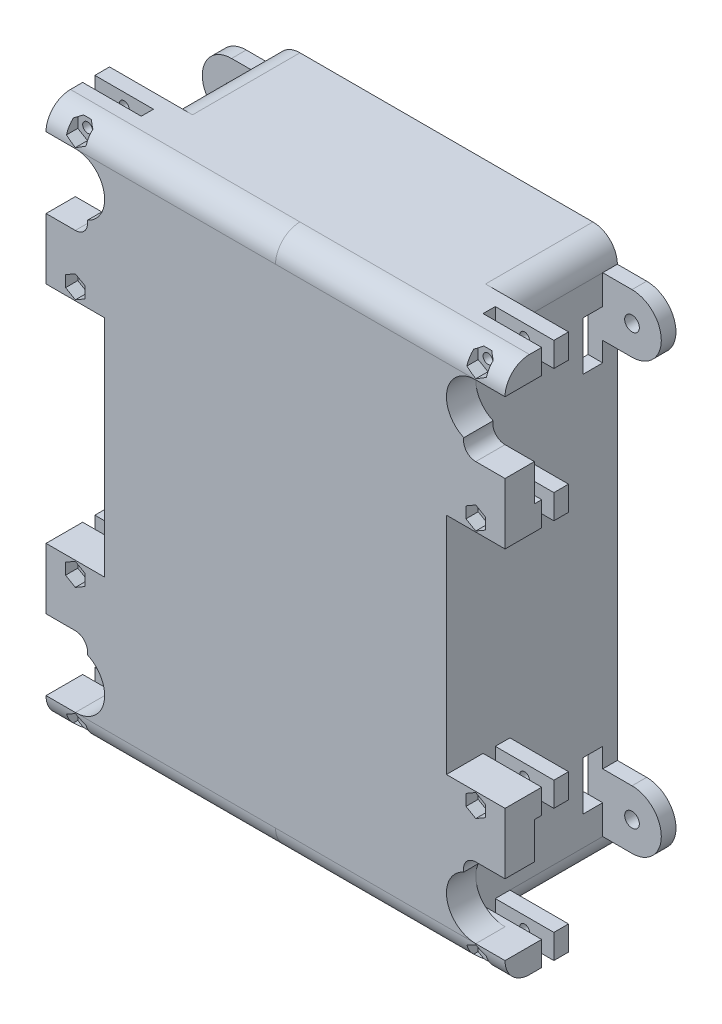
SolidWorks part; units mm, degrees
other "标注1"
sketch "草图35" plane through (-29.5, -27.5, 0) normal (-1, 0, 0) x (0, 1, 0)
ref_plane "前视基准面" through (0, 0, 0) normal (0, 0, 1) x (1, 0, 0)
ref_plane "上视基准面" through (0, 0, 0) normal (0, 1, 0) x (1, 0, 0)
ref_plane "右视基准面" through (0, 0, 0) normal (1, 0, 0) x (0, 0, -1)
sketch "草图3" plane through (0, 0, 0) normal (0, 0, 1) x (1, 0, 0)
  line L1 (17.5, -27.5) -> (-17.5, -27.5)
  line L2 (17.5, -27.5) -> (17.5, 27.5)
  line L3 (17.5, 27.5) -> (-17.5, 27.5)
  line L4 (-17.5, -27.5) -> (-17.5, -4.5)
  line L7 (-17.5, 27.5) -> (-29.5, 27.5)
  line L9 (-17.5, -4.5) -> (-29.5, -4.5)
  line L10 (-29.5, 27.5) -> (-29.5, -4.5)
  point P0 (0, 0)
  dimension "D1" = 55
  dimension "D2" = 35
  dimension "D3" = 32
  dimension "D4" = 12
extrude "凸台-拉伸3" add sketch "草图3" along normal blind 35
sketch "草图4" plane through (0, 0, 35) normal (0, 0, 1) x (1, 0, 0)
  line L1 (17.5, -27.5) -> (-12.5, -27.5)
  line L2 (17.5, -27.5) -> (17.5, 22.5)
  line L3 (17.5, 22.5) -> (-12.5, 22.5)
  line L4 (-12.5, -27.5) -> (-12.5, 22.5)
  dimension "D1" = 50
  dimension "D2" = 30
extrude "切除-拉伸1" cut sketch "草图4" against normal through all
sketch "草图5" plane through (0, 0, 35) normal (0, 0, 1) x (1, 0, 0)
  line L0 (-23.5, 22.5) -> (-29.5, 22.5)
  line L9 (-23.5, 8) -> (-29.5, 8)
  line L10 (-29.5, 27.5) -> (-29.5, -4.5) construction
  circle A1 centre (-23.5, 16.5) radius 1.25
  arc A2 (-21.0549, 11.0208) -> (-23.5, 22.5) centre (-23.5, 16.5) ccw
  arc A3 (-23.5, 8) -> (-21.0549, 11.0208) centre (-23.5, 10.5) ccw
  line M14 (-29.5, 27.5) -> (-29.5, -4.5)
  dimension "D7" = 2.5
  dimension "D1" = 5
  dimension "D6" = 6
extrude "切除-拉伸5" cut sketch "草图5" against normal blind 6 contours L9 A3 A2 L0 A1 M14 region at (-24.2708, 15.4863, 35)
sketch "草图6" plane through (0, 0, 35) normal (0, 0, 1) x (1, 0, 0)
  circle A0 centre (-23.5, 16.5) radius 1.25
extrude "切除-拉伸6" cut sketch "草图6" against normal through all
sketch "草图7" plane through (0, 0, 29) normal (0, 0, 1) x (1, 0, 0)
  line L1 (-29.5, 27.5) -> (-17.5, 27.5)
  line L2 (-29.5, 27.5) -> (-29.5, -4.5)
  line L3 (-29.5, -4.5) -> (-17.5, -4.5)
  line L4 (-17.5, 27.5) -> (-17.5, -4.5)
  dimension "D1" = 32
  dimension "D2" = 12
extrude "切除-拉伸7" cut sketch "草图7" against normal blind 4
sketch "草图9" plane through (0, 0, 25) normal (0, 0, 1) x (1, 0, 0)
  line L1 (-29.5, 22.5) -> (-17.5, 22.5)
  line L2 (-29.5, 22.5) -> (-29.5, 0.5)
  line L3 (-29.5, 0.5) -> (-17.5, 0.5)
  line L4 (-17.5, 22.5) -> (-17.5, 0.5)
  dimension "D1" = 22
  dimension "D2" = 12
extrude "切除-拉伸9" cut sketch "草图9" against normal blind 22
sketch "草图10" plane through (-29.5, 0, 0) normal (-1, 0, 0) x (0, 0, 1)
  line L1 (24, -4.5) -> (6, -4.5)
  line L2 (24, -4.5) -> (24, 27.5)
  line L3 (24, 27.5) -> (6, 27.5)
  line L4 (6, -4.5) -> (6, 27.5)
  line L6 (25, -4.5) -> (0, -4.5) construction
  line L7 (25, 27.5) -> (0, 27.5) construction
  dimension "D1" = 32
  dimension "D2" = 18
extrude "切除-拉伸10" cut sketch "草图10" against normal blind 12
sketch "草图11" plane through (0, 0, 3) normal (0, 0, 1) x (1, 0, 0)
  circle A0 centre (-23.5, 16.5) radius 1.5
  dimension "D1" = 3
extrude "切除-拉伸11" cut sketch "草图11" against normal blind 12
sketch "草图14" plane through (-17.5, 0, 0) normal (-1, 0, 0) x (0, 0, 1)
  line L1 (29, 27.5) -> (27.5, 27.5)
  line L2 (29, 27.5) -> (29, 22.5)
  line L3 (29, 22.5) -> (27.5, 22.5)
  line L4 (27.5, 27.5) -> (27.5, 22.5)
  line L5 (29, -4.5) -> (27.5, -4.5)
  line L6 (29, -4.5) -> (29, 0.5)
  line L7 (29, 0.5) -> (27.5, 0.5)
  line L8 (27.5, -4.5) -> (27.5, 0.5)
  dimension "D1" = 5
  dimension "D2" = 1.5
  dimension "D3" = 5
  dimension "D4" = 1.5
extrude "凸台-拉伸4" add sketch "草图14" along normal blind 12
sketch "草图15" plane through (0, 0, 6) normal (0, 0, 1) x (1, 0, 0)
  line L1 (-17.5, 27.5) -> (-29.5, 27.5)
  line L2 (-17.5, 27.5) -> (-17.5, 22.5)
  line L3 (-17.5, 22.5) -> (-29.5, 22.5)
  line L4 (-29.5, 27.5) -> (-29.5, 22.5)
  line L5 (-17.5, 0.5) -> (-29.5, 0.5)
  line L6 (-17.5, 0.5) -> (-17.5, -4.5)
  line L7 (-17.5, -4.5) -> (-29.5, -4.5)
  line L8 (-29.5, 0.5) -> (-29.5, -4.5)
  dimension "D1" = 5
  dimension "D2" = 12
  dimension "D3" = 5
  dimension "D4" = 12
extrude "切除-拉伸15" cut sketch "草图15" against normal blind 12
sketch "草图16" plane through (0, 0, 24) normal (0, 0, -1) x (-1, 0, 0)
  line L1 (17.5, 27.5) -> (29.5, 27.5)
  line L2 (17.5, 27.5) -> (17.5, 22.5)
  line L3 (17.5, 22.5) -> (29.5, 22.5)
  line L4 (29.5, 27.5) -> (29.5, 22.5)
  line L5 (29.5, 0.5) -> (17.5, 0.5)
  line L6 (29.5, 0.5) -> (29.5, -4.5)
  line L7 (29.5, -4.5) -> (17.5, -4.5)
  line L8 (17.5, 0.5) -> (17.5, -4.5)
  dimension "D1" = 5
  dimension "D2" = 12
  dimension "D3" = 5
  dimension "D4" = 12
extrude "凸台-拉伸5" add sketch "草图16" along normal blind 2
sketch "草图17" plane through (0, 0, 22) normal (0, 0, -1) x (-1, 0, 0)
  line L0 (29.5, 27.5) -> (17.5, 27.5) construction
  line L1 (17.5, 22.5) -> (17.5, 27.5) construction
  line L2 (-970.5, 11.5) -> (49029.5, 11.5) construction
  line L3 (29.5, 22.5) -> (29.5, 0.5) construction
  circle A0 centre (23.5, 25) radius 1
  circle A1 centre (23.5, -2) radius 1
  point P11 (29.5, 11.5)
  dimension "D1" = 2.5
  dimension "D2" = 6
  dimension "D3" = 2
extrude "切除-拉伸16" cut sketch "草图17" against normal through all
sketch "草图18" plane through (-12.5, 0, 0) normal (1, 0, 0) x (0, 0, -1)
  line L1 (-35, 22.5) -> (-30, 22.5)
  line L2 (-35, 22.5) -> (-35, -27.5)
  line L3 (-35, -27.5) -> (-30, -27.5)
  line L4 (-30, 22.5) -> (-30, -27.5)
  line L5 (0, -27.5) -> (-35, -27.5) construction
  dimension "D1" = 50
  dimension "D2" = 5
extrude "凸台-拉伸6" add sketch "草图18" along normal blind 30
sketch "草图19" plane through (-17.5, 0, 0) normal (-1, 0, 0) x (0, 0, 1)
  line L0 (3, 11.5) -> (50003, 11.5) construction
  line L1 (3, 0.5) -> (3, 22.5) construction
  line L3 (3, 16.5) -> (7, 16.5)
  line L4 (3, 16.5) -> (3, 6.5)
  line L5 (3, 6.5) -> (7, 6.5)
  line L6 (7, 16.5) -> (7, 6.5)
  point P4 (3, 11.5)
  dimension "D1" = 10
  dimension "D2" = 4
  dimension "D3" = 5
extrude "切除-拉伸17" cut sketch "草图19" against normal blind 30
fillet "圆角1" radius 5 1 edges at (-17.5, 27.5, 11)
sketch "草图20" plane through (0, 0, 3) normal (0, 0, 1) x (1, 0, 0)
  line L1 (-29.5, 0.5) -> (-17.5, 0.5)
  line L2 (-29.5, 0.5) -> (-29.5, 6.5)
  line L3 (-29.5, 6.5) -> (-17.5, 6.5)
  line L4 (-17.5, 0.5) -> (-17.5, 6.5)
  dimension "D1" = 6
  dimension "D2" = 12
extrude "切除-拉伸18" cut sketch "草图20" against normal blind 30
sketch "草图21" plane through (0, 0, 30) normal (0, 0, -1) x (-1, 0, 0)
  line L1 (-17.5, -27.5) -> (14.5, -27.5)
  line L2 (-17.5, -27.5) -> (-17.5, 24.5)
  line L3 (-17.5, 24.5) -> (14.5, 24.5)
  line L4 (14.5, -27.5) -> (14.5, 24.5)
  dimension "D1" = 52
  dimension "D2" = 32
extrude "切除-拉伸19" cut sketch "草图21" along normal blind 54
fillet "圆角3" radius 5 1 edges at (-6, 27.5, 35)
sketch "草图23" plane through (0, 0, 0) normal (0, 0, -1) x (-1, 0, 0)
  line L1 (29.5, 22.5) -> (17.5, 22.5) construction
  line L2 (29.5, 22.5) -> (29.5, 6.5) construction
  line L3 (23.5, 22.5) -> (29.5, 22.5)
  line L4 (29.5, 22.5) -> (29.5, 16.5)
  arc A0 (29.5, 16.5) -> (23.5, 22.5) centre (23.5, 16.5) ccw
extrude "切除-拉伸21" cut sketch "草图23" against normal blind 12
sketch "草图24" plane through (0, 0, 0) normal (0, 0, -1) x (-1, 0, 0)
  line L0 (17.5, 6.5) -> (17.5, 10.5)
  line L1 (23.5, 10.5) -> (17.5, 10.5)
  line L2 (29.5, 16.5) -> (29.5, 6.5) construction
  line L3 (17.5, 6.5) -> (29.5, 6.5)
  line L4 (29.5, 6.5) -> (29.5, 16.5)
  arc A0 (23.5, 10.5) -> (29.5, 16.5) centre (23.5, 16.5) ccw
extrude "切除-拉伸22" cut sketch "草图24" against normal blind 12
sketch "草图26" plane through (-14.5, 0, 0) normal (1, 0, 0) x (0, 0, -1)
  line L1 (-7, 16.5) -> (-3, 16.5)
  line L2 (-7, 16.5) -> (-7, 24.5)
  line L3 (-7, 24.5) -> (-3, 24.5)
  line L4 (-3, 16.5) -> (-3, 24.5)
  line L5 (0, 24.5) -> (-30, 24.5) construction
  dimension "D1" = 8
  dimension "D2" = 4
extrude "凸台-拉伸7" add sketch "草图26" along normal blind 8
sketch "草图27" plane through (0, 0, 3) normal (0, 0, -1) x (-1, 0, 0)
  line L0 (6.5, 24.5) -> (14.5, 24.5) construction
  line L1 (14.5, 16.5) -> (14.5, 24.5) construction
  circle A0 centre (10.5, 20.5) radius 1.5
  dimension "D1" = 3
  dimension "D2" = 4
  dimension "D3" = 4
extrude "切除-拉伸23" cut sketch "草图27" against normal blind 8
sketch "草图32" plane through (0, 0, 3) normal (0, 0, -1) x (-1, 0, 0)
  line L0 (6.5, 20.5) -> (6.5, 16.5)
  line L1 (6.5, 16.5) -> (10.5, 16.5)
  line L2 (6.5, 24.5) -> (6.5, 20.5)
  line L3 (10.5, 24.5) -> (6.5, 24.5)
  arc A0 (6.5, 20.5) -> (10.5, 16.5) centre (10.5, 20.5) ccw
  arc A1 (10.5, 24.5) -> (10.5, 16.5) centre (10.5, 20.5) ccw
  line M6 (14.5, 24.5) -> (6.5, 24.5)
  line M7 (6.5, 24.5) -> (6.5, 16.5)
extrude "切除-拉伸25" cut sketch "草图32" against normal blind 10 contours A1 M6 M7 region at (-7.3935, 23.6065, 3)
sketch "草图33" plane through (0, 0, 3) normal (0, 0, -1) x (-1, 0, 0)
  line L0 (6.5, 20.5) -> (6.5, 16.5)
  line L1 (6.5, 16.5) -> (10.5, 16.5)
  arc A0 (6.5, 20.5) -> (10.5, 16.5) centre (10.5, 20.5) ccw
extrude "切除-拉伸26" cut sketch "草图33" against normal blind 10
sketch "草图34" plane through (0, 0, 7) normal (0, 0, 1) x (1, 0, 0)
  line L0 (-14.5, 24.5) -> (-14.5, 16.5) construction
  line L1 (-10.5, 17.44) -> (-7.85, 18.97)
  line L2 (-7.85, 18.97) -> (-7.85, 22.03)
  line L3 (-7.85, 22.03) -> (-10.5, 23.56)
  line L4 (-10.5, 23.56) -> (-13.15, 22.03)
  line L5 (-13.15, 22.03) -> (-13.15, 18.97)
  line L6 (-13.15, 18.97) -> (-10.5, 17.44)
  circle A0 centre (-10.5, 20.5) radius 2.65 construction
  dimension "D1" = 5.3
extrude "切除-拉伸27" cut sketch "草图34" against normal blind 2
sketch "草图36" plane through (0, 0, 35) normal (0, 0, 1) x (1, 0, 0)
  line L0 (-29.5, 8) -> (-29.5, -4.5) construction
  line L1 (-23.5, 27.3094) -> (-25.5, 26.1547)
  line L2 (-25.5, 26.1547) -> (-25.5, 23.8453)
  line L3 (-25.5, 23.8453) -> (-23.5, 22.6906)
  line L4 (-23.5, 22.6906) -> (-21.5, 23.8453)
  line L5 (-21.5, 23.8453) -> (-21.5, 26.1547)
  line L6 (-21.5, 26.1547) -> (-23.5, 27.3094)
  line L7 (-23.5, 0.3094) -> (-25.5, -0.8453)
  line L8 (-25.5, -0.8453) -> (-25.5, -3.1547)
  line L9 (-25.5, -3.1547) -> (-23.5, -4.3094)
  line L10 (-23.5, -4.3094) -> (-21.5, -3.1547)
  line L11 (-21.5, -3.1547) -> (-21.5, -0.8453)
  line L12 (-21.5, -0.8453) -> (-23.5, 0.3094)
  line L13 (-29.5, 27.5) -> (-29.5, 22.5) construction
  circle A0 centre (-23.5, 25) radius 2 construction
  circle A1 centre (-23.5, -2) radius 2 construction
  dimension "D1" = 4
  dimension "D2" = 4
extrude "切除-拉伸28" cut sketch "草图36" against normal blind 2.5
sketch "草图37" plane through (0, 0, 22) normal (0, 0, -1) x (-1, 0, 0)
  circle A0 centre (23.5, 25) radius 1.5
  circle A1 centre (23.5, -2) radius 1.5
  dimension "D1" = 3
extrude "切除-拉伸29" cut sketch "草图37" against normal blind 1
mirror "镜向5" about plane through (17.5, -27.5, 35) normal (0, 1, 0) of "切除-拉伸1", "切除-拉伸5", "切除-拉伸6", "切除-拉伸7", "切除-拉伸9", "切除-拉伸10", "切除-拉伸11", "凸台-拉伸4", "切除-拉伸15", "凸台-拉伸5", "切除-拉伸16", "凸台-拉伸6", "切除-拉伸17", "圆角1", "切除-拉伸18", "切除-拉伸19", "圆角3", "切除-拉伸21", "切除-拉伸22", "凸台-拉伸7", "切除-拉伸23", "切除-拉伸25", "切除-拉伸26", "切除-拉伸27", "切除-拉伸28", "凸台-拉伸3", "切除-拉伸29"
ref_plane "基准面12" through (17.5, 0, 0) normal (-1, 0, 0) x (0, 0, 1)
mirror "镜向8" about plane through (17.5, 0, 0) normal (-1, 0, 0) of "切除-拉伸1", "切除-拉伸5", "切除-拉伸6", "切除-拉伸7", "切除-拉伸9", "切除-拉伸10", "切除-拉伸11", "凸台-拉伸4", "切除-拉伸15", "凸台-拉伸5", "切除-拉伸16", "凸台-拉伸6", "切除-拉伸17", "圆角1", "切除-拉伸18", "切除-拉伸19", "圆角3", "切除-拉伸21", "切除-拉伸22", "凸台-拉伸7", "切除-拉伸23", "切除-拉伸25", "切除-拉伸26", "切除-拉伸27", "切除-拉伸28", "凸台-拉伸3", "切除-拉伸29"
pattern_circular "阵列(圆周)1" count 2 over 360 about axis through (17.5, -27.5, 35) along (0, 0, -1) of "凸台-拉伸3", "切除-拉伸28", "切除-拉伸27", "切除-拉伸26", "切除-拉伸25", "切除-拉伸23", "凸台-拉伸7", "切除-拉伸22", "切除-拉伸21", "圆角3", "切除-拉伸19", "切除-拉伸18", "圆角1", "切除-拉伸17", "凸台-拉伸6", "切除-拉伸16", "凸台-拉伸5", "切除-拉伸15", "凸台-拉伸4", "切除-拉伸11", "切除-拉伸10", "切除-拉伸9", "切除-拉伸7", "切除-拉伸6", "切除-拉伸5", "切除-拉伸1", "切除-拉伸29"
